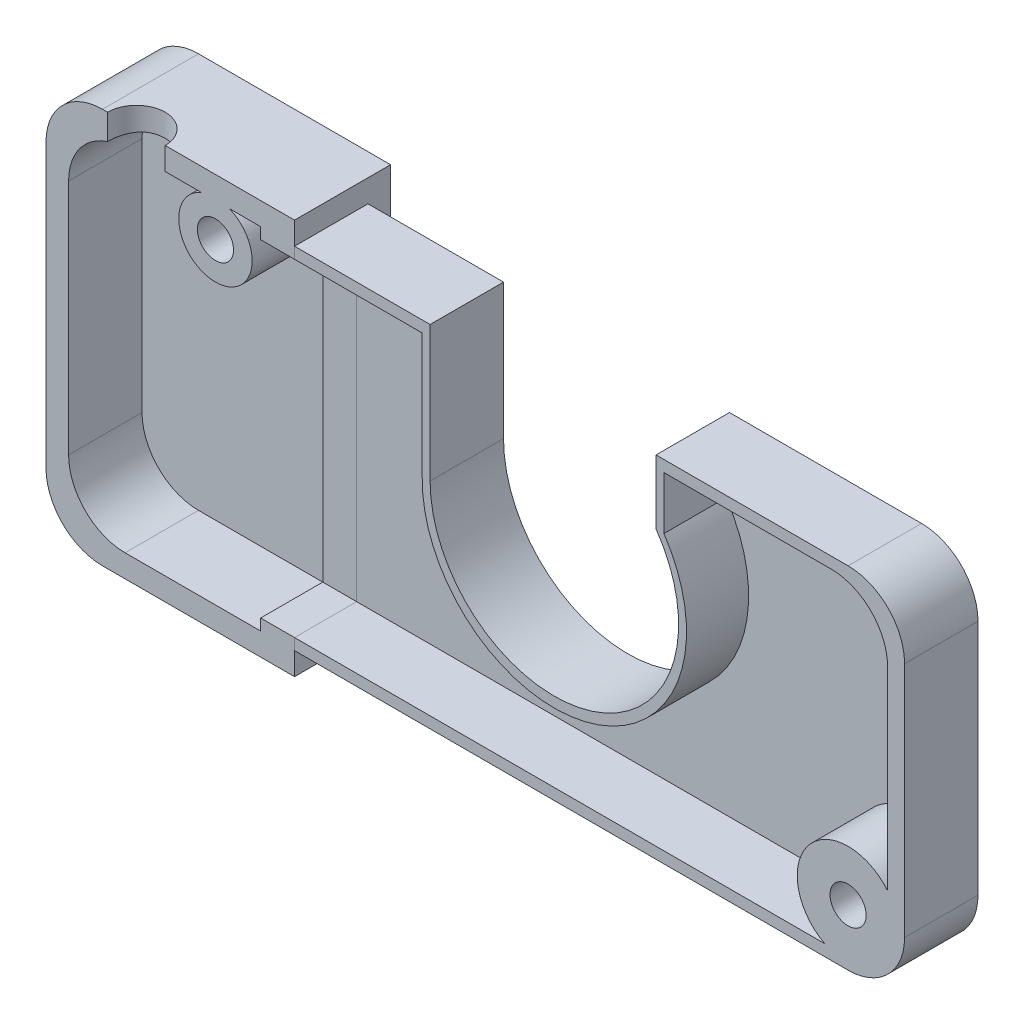
SolidWorks part; units mm, degrees
ref_plane "Front Plane" through (0, 0, 0) normal (0, 0, 1) x (1, 0, 0)
ref_plane "Top Plane" through (0, 0, 0) normal (0, 1, 0) x (1, 0, 0)
ref_plane "Right Plane" through (0, 0, 0) normal (1, 0, 0) x (0, 0, -1)
sketch "Sketch1" plane through (0, 0, 0) normal (0, 0, 1) x (1, 0, 0)
  line L0 (0, 21) -> (78, 21) construction
  line L1 (5, 0) -> (73, 0)
  line L2 (0, 5) -> (0, 30)
  line L3 (5, 35) -> (73, 35)
  line L4 (78, 5) -> (78, 30)
  line L5 (45, 35) -> (45, 0) construction
  line L6 (34, 21) -> (34, 35)
  line L7 (54, 35) -> (54, 27.3246)
  line L11 (22, 35) -> (22, 0) construction
  arc A0 (34, 21) -> (54, 27.3246) centre (45, 21) ccw
  arc A1 (5, 0) -> (0, 5) centre (5, 5) cw
  arc A2 (0, 30) -> (5, 35) centre (5, 30) cw
  arc A3 (73, 0) -> (78, 5) centre (73, 5) ccw
  arc A4 (78, 30) -> (73, 35) centre (73, 30) ccw
  point P18 (0, 0)
  point P21 (0, 35)
  point P24 (78, 0)
  dimension "D5" = 22
  dimension "D8" = 5
  dimension "D1" = 35
  dimension "D2" = 34
  dimension "D3" = 21
  dimension "D4" = 24
  dimension "D6" = 20
  dimension "D7" = 12
extrude "Boss-Extrude1" add sketch "Sketch1" along normal blind 17 contours L4 A4 L3 L7 A0 L6 A2 L2 A1 L1 A3 region at (2.069, 2.069, 0)
sketch "Sketch3" plane through (0, 0, 17) normal (0, 0, 1) x (1, 0, 0)
  line L0 (78, 5) -> (78, 30) construction
  line L1 (71, 33) -> (21, 33)
  line L2 (76, 28) -> (76, 7)
  line L3 (71, 2) -> (21, 2)
  line L4 (21, 33) -> (21, 2)
  line L6 (5, 0) -> (73, 0) construction
  line L7 (54, 35) -> (73, 35) construction
  line L8 (34, 21) -> (34, 35) construction
  line L9 (5, 35) -> (34, 35) construction
  line L10 (22, 35) -> (78, 35)
  line L11 (22, 35) -> (22, 0)
  line L12 (22, 0) -> (78, 0)
  line L13 (78, 35) -> (78, 0)
  arc A0 (71, 2) -> (76, 7) centre (71, 7) ccw
  arc A1 (76, 28) -> (71, 33) centre (71, 28) ccw
  line M9 (78, 5) -> (78, 30)
  arc M10 (78, 30) -> (73, 35) centre (73, 30) ccw
  line M11 (73, 35) -> (54, 35)
  line M12 (54, 35) -> (54, 27.3246)
  arc M13 (54, 27.3246) -> (34, 21) centre (45, 21) cw
  line M14 (34, 21) -> (34, 35)
  line M15 (34, 35) -> (5, 35)
  line M19 (5, 0) -> (73, 0)
  arc M20 (73, 0) -> (78, 5) centre (73, 5) ccw
  dimension "D5" = 5
  dimension "D1" = 2
  dimension "D2" = 2
  dimension "D3" = 2
  dimension "D4" = 13
  dimension "D6" = 2
  dimension "D7" = 2
  dimension "D8" = 12
extrude "Cut-Extrude1" cut sketch "Sketch3" against normal blind 17 contours L11 L1 M15 M14 | A1 L2 A0 L3 L11 L1 M19 M20 M9 M10 M11 M12 region at (62.5, 33.6604, 17) region at (28, 34, 17)
extrude "Cut-Extrude2" cut sketch "Sketch3<3>" against normal blind 2 contours L2 A1 L1 L4 L3 A0 M12 M13 M14 region at (74.0952, 31.0952, 17)
sketch "Sketch3<3>" plane through (0, 0, 17) normal (0, 0, 1) x (1, 0, 0) same geometry as "Sketch3"
sketch "Sketch5" plane through (0, 0, 0) normal (0, 0, -1) x (-1, 0, 0)
  line L1 (-22, 33) -> (-82, 33)
  line L2 (-22, 33) -> (-22, -2)
  line L3 (-22, -2) -> (-82, -2)
  line L4 (-82, 33) -> (-82, -2)
  dimension "D1" = 60
  dimension "D2" = 35
extrude "Cut-Extrude3" cut sketch "Sketch5" against normal blind 2
ref_plane "Plane1" through (0, 0, 14) normal (0, 0, 1) x (1, 0, 0)
sketch "Sketch6" plane through (0, 0, 14) normal (0, 0, 1) x (1, 0, 0)
  line L0 (22, 35) -> (22, 0) construction
  line L1 (22, 32) -> (69.5, 32)
  line L2 (22, 32) -> (22, 3)
  line L3 (22, 3) -> (69.5, 3)
  line L4 (74.5, 27) -> (74.5, 8)
  line L5 (76, 28) -> (76, 7) construction
  line L6 (71, 2) -> (22, 2) construction
  line L7 (71, 33) -> (54, 33) construction
  arc A0 (69.5, 3) -> (74.5, 8) centre (69.5, 8) ccw
  arc A1 (74.5, 27) -> (69.5, 32) centre (69.5, 27) ccw
  dimension "D4" = 5
  dimension "D1" = 1.5
  dimension "D2" = 1
  dimension "D3" = 1
extrude "Cut-Extrude4" cut sketch "Sketch6" against normal blind 11
sketch "Sketch11" plane through (0, 0, 15) normal (0, 0, 1) x (1, 0, 0)
  line L0 (0, 5) -> (0, 30) construction
  line L1 (22, 2) -> (7, 2)
  line L2 (22, 2) -> (22, 33)
  line L3 (22, 33) -> (7, 33)
  line L4 (2, 7) -> (2, 28)
  arc A0 (7, 2) -> (2, 7) centre (7, 7) cw
  arc A1 (7, 33) -> (2, 28) centre (7, 28) ccw
  dimension "D3" = 5
  dimension "D1" = 2
  dimension "D2" = 31
extrude "Cut-Extrude11" cut sketch "Sketch11" against normal blind 13
sketch "Sketch12" plane through (0, 0, 15) normal (0, 0, 1) x (1, 0, 0)
  line L0 (22, 33) -> (22, 2) construction
  line L1 (39.5, 5.75) -> (40.7, 5.75)
  line L2 (39, 5.25) -> (39, 4.75)
  line L3 (39.5, 4.25) -> (40.7, 4.25)
  line L4 (41.2, 5.25) -> (41.2, 4.75)
  line L7 (5, 0) -> (22, 0) construction
  arc A0 (41.2, 4.75) -> (40.7, 4.25) centre (40.7, 4.75) cw
  arc A1 (41.2, 5.25) -> (40.7, 5.75) centre (40.7, 5.25) ccw
  arc A2 (39, 4.75) -> (39.5, 4.25) centre (39.5, 4.75) ccw
  arc A3 (39, 5.25) -> (39.5, 5.75) centre (39.5, 5.25) cw
  point P10 (41.2, 4.25)
  point P15 (39, 4.25)
  point P18 (39, 5.75)
  dimension "D5" = 0.5
  dimension "D1" = 2.2
  dimension "D2" = 1.5
  dimension "D3" = 17
  dimension "D4" = 5.75
extrude "Boss-Extrude2" add sketch "Sketch12" along normal blind 2
sketch "Sketch13" plane through (0, 0, 17) normal (0, 0, 1) x (1, 0, 0)
  line L0 (5, 35) -> (5, 0) construction
  line L1 (5, 35) -> (22, 35) construction
  line L2 (5, 0) -> (22, 0) construction
  line L3 (0, 5) -> (0, 30) construction
  line L4 (0, 7) -> (22, 7) construction
  line L5 (22, 33) -> (22, 2) construction
  circle A0 centre (5, 7) radius 2.5
  dimension "D1" = 5
  dimension "D2" = 5
  dimension "D3" = 28
extrude "Cut-Extrude12" cut sketch "Sketch13" against normal blind 5
sketch "Sketch14" plane through (0, 35, 0) normal (0, 1, 0) x (1, 0, 0)
  line L0 (5, -8.5) -> (22, -8.5) construction
  line L1 (5, -17) -> (5, 0) construction
  line L2 (22, -2) -> (22, -15) construction
  line L3 (8, 0) -> (8, -17) construction
  line L6 (5, 0) -> (22, 0) construction
  line L7 (5, -17) -> (22, -17) construction
  line L8 (0, -17) -> (0, 0) construction
  circle A1 centre (8, -8.5) radius 2.55
  dimension "D2" = 5.1
  dimension "D1" = 8
extrude "Cut-Extrude14" cut sketch "Sketch14" against normal blind 15
sketch "Sketch15" plane through (0, 0, 17) normal (0, 0, 1) x (1, 0, 0)
  line L0 (15, 35) -> (15, 0) construction
  line L1 (5, 35) -> (22, 35) construction
  line L2 (5, 0) -> (22, 0) construction
  line L3 (0, 30) -> (22, 30) construction
  line L4 (0, 5) -> (0, 30) construction
  line L5 (22, 33) -> (22, 2) construction
  circle A0 centre (15, 30) radius 3.25
  circle A1 centre (15, 30) radius 1.6
  dimension "D3" = 6.5
  dimension "D4" = 3.2
  dimension "D1" = 15
  dimension "D2" = 5
extrude "Boss-Extrude5" add sketch "Sketch15" against normal through all
extrude "Cut-Extrude16" cut sketch "Sketch15<4>" against normal blind 1
sketch "Sketch15<4>" plane through (0, 0, 17) normal (0, 0, 1) x (1, 0, 0) same geometry as "Sketch15"
sketch "Sketch18" plane through (0, 0, 17) normal (0, 0, 1) x (1, 0, 0)
  circle A0 centre (15, 30) radius 1.6
  dimension "D1" = 3.2
extrude "Cut-Extrude17" cut sketch "Sketch18" against normal blind 15
sketch "Sketch20" plane through (0, 0, 15) normal (0, 0, 1) x (1, 0, 0)
  line L0 (71, 33) -> (71, 2) construction
  line L1 (71, 33) -> (54, 33) construction
  line L2 (71, 2) -> (22, 2) construction
  line L3 (76, 7) -> (22, 7) construction
  line L4 (22, 33) -> (22, 2) construction
  line L5 (76, 28) -> (76, 7) construction
  arc A0 (71, 2) -> (76, 7) centre (71, 7) ccw construction
  circle A1 centre (71, 7) radius 4.5
  circle A2 centre (71, 7) radius 1.6
  dimension "D3" = 9
  dimension "D4" = 3.2
  dimension "D1" = 5
  dimension "D2" = 5
extrude "Boss-Extrude6" add sketch "Sketch20" against normal blind 13
extrude "Cut-Extrude20" cut sketch "Sketch20<3>" against normal through all from surface contours A2 starting at face at (52.0388, 20.5674, 15)
sketch "Sketch20<3>" plane through (0, 0, 15) normal (0, 0, 1) x (1, 0, 0) same geometry as "Sketch20"
sketch "Sketch21" plane through (0, 0, 2) normal (0, 0, -1) x (-1, 0, 0)
  circle A0 centre (-71, 7) radius 3.5
  dimension "D1" = 7
ref_plane "Plane13" through (0, 0, 8.5) normal (0, 0, 1) x (1, 0, 0)
sketch "Sketch22" plane through (22, 0, 0) normal (1, 0, 0) x (0, 0, -1)
  line L0 (-2, 2) -> (-15, 2) construction
  line L1 (-15, 33) -> (-2, 33)
  line L2 (-15, 33) -> (-15, 2)
  line L3 (-15, 2) -> (-2, 2)
  line L4 (-2, 33) -> (-2, 2)
  line L5 (-2, 2) -> (-15, 2) construction
  line L6 (-14, 17.05) -> (-14, -17.05) construction
  line L11 (-14, 32) -> (-3, 32)
  line L12 (-14, 32) -> (-14, 3)
  line L13 (-14, 3) -> (-3, 3)
  line L14 (-3, 32) -> (-3, 3)
  line L15 (0, 35) -> (0, 0) construction
  dimension "D1" = 2
  dimension "D2" = 1
  dimension "D3" = 1
  dimension "D4" = 1
extrude "Boss-Extrude7" add sketch "Sketch22" against normal blind 3
sketch "Sketch24" plane through (0, 0, 8.5) normal (0, 0, 1) x (1, 0, 0)
  line L1 (0, 0) -> (80, 0)
  line L2 (0, 0) -> (0, 36)
  line L3 (0, 36) -> (80, 36)
  line L4 (80, 0) -> (80, 36)
  dimension "D1" = 36
  dimension "D2" = 80
extrude "Cut-Extrude21" cut sketch "Sketch21" against normal blind 2
sketch "Sketch29" plane through (0, 0, 15) normal (0, 0, 1) x (1, 0, 0)
  circle A0 centre (71, 7) radius 3.5
  dimension "D1" = 7
extrude "Cut-Extrude22" cut sketch "Sketch29" against normal blind 2.5
sketch "Sketch36" plane through (0, 0, 15) normal (0, 0, 1) x (1, 0, 0)
  line L0 (34, 33) -> (34, 21)
  line L1 (54, 27.3246) -> (54, 33)
  line L2 (54, 33) -> (54.7, 33)
  line L3 (71, 33) -> (54, 33) construction
  line L4 (54.7, 33) -> (54.7, 27.3246)
  line L5 (33.3, 21) -> (33.3, 33)
  line L6 (34, 33) -> (22, 33) construction
  line L7 (33.3, 33) -> (34, 33)
  line L15 (76, 7) -> (76, 28)
  line L16 (71, 33) -> (54, 33)
  line L17 (54, 33) -> (54, 27.3246)
  line L18 (34, 21) -> (34, 33)
  line L19 (34, 33) -> (22, 33)
  line L20 (22, 33) -> (22, 2)
  line L21 (22, 2) -> (71, 2)
  line L23 (54.7, 33) -> (54, 33)
  line L24 (54, 33) -> (54, 27.3246)
  line L25 (34, 21) -> (34, 33)
  line L26 (34, 33) -> (33.3, 33)
  arc A2 (33.3, 21) -> (54.7, 27.3246) centre (44.998, 20.7853) ccw
  arc A4 (34, 21) -> (54, 27.3246) centre (45, 21) ccw
  arc A7 (76, 28) -> (71, 33) centre (71, 28) ccw
  arc A8 (34, 21) -> (54, 27.3246) centre (45, 21) ccw
  arc A9 (71, 2) -> (76, 7) centre (71, 7) ccw
  line M9 (71, 33) -> (54, 33)
  line M10 (54, 33) -> (54, 27.3246)
  arc M11 (54, 27.3246) -> (34, 21) centre (45, 21) cw
  line M12 (34, 21) -> (34, 33)
  line M13 (34, 33) -> (22, 33)
  dimension "D3" = 11.7
  dimension "D1" = 0.7
  dimension "D2" = 0.7
  dimension "D4" = 0
extrude "Boss-Extrude10" add sketch "Sketch36" against normal up to surface (13 mm away) contours L5 A2 L4 M9 M10 M11 M12 M13 region at (33.6654, 27, 15) up to face at (67.5, 7, 2)
extrude "Cut-Extrude23" cut sketch "Sketch24" along normal blind 10
